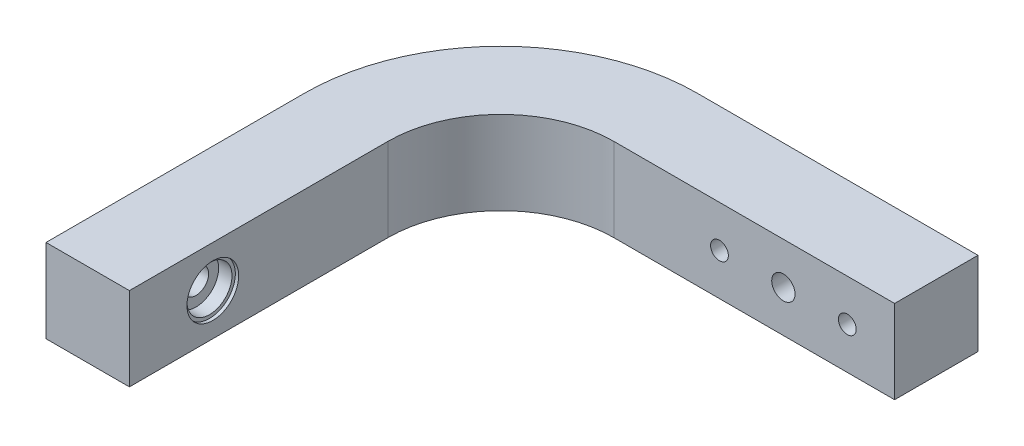
SolidWorks part; units mm, degrees
ref_plane "Front Plane" through (0, 0, 0) normal (0, 0, 1) x (1, 0, 0)
ref_plane "Top Plane" through (0, 0, 0) normal (0, 1, 0) x (1, 0, 0)
ref_plane "Right Plane" through (0, 0, 0) normal (1, 0, 0) x (0, 0, -1)
ref_axis "Z" through (0, 0, -59.2654) along (0, 0, 1)
sketch "Sketch1" plane through (0, 0, 0) normal (0, 1, 0) x (1, 0, 0)
  line L0 (-30.4827, 0) -> (30.4827, 0) construction
  line L1 (-65.8046, -35.3218) -> (-65.8046, -81.8046)
  line L2 (-65.8046, -81.8046) -> (-50.8046, -81.8046)
  line L3 (-50.8046, -81.8046) -> (-50.8046, -35.3218)
  line L4 (-30.4827, -15) -> (30.4827, -15) construction
  line L5 (0, -15) -> (0, 0) construction
  line L6 (50.8046, -81.8046) -> (50.8046, -35.3218) construction
  line L7 (65.8046, -81.8046) -> (50.8046, -81.8046) construction
  line L8 (65.8046, -35.3218) -> (65.8046, -81.8046) construction
  line L9 (30.4827, 0) -> (30.4827, -15) construction
  line L10 (20, -15) -> (20, 0)
  line L11 (-30.4827, -15) -> (20, -15)
  line L12 (-30.4827, 0) -> (20, 0)
  line L13 (0, 59.2654) -> (0, -30.9346) construction
  arc A0 (-30.4827, 0) -> (-65.8046, -35.3218) centre (-30.4827, -35.3218) ccw
  arc A1 (-50.8046, -35.3218) -> (-30.4827, -15) centre (-30.4827, -35.3218) cw
  arc A2 (50.8046, -35.3218) -> (30.4827, -15) centre (30.4827, -35.3218) ccw construction
  arc A3 (30.4827, 0) -> (65.8046, -35.3218) centre (30.4827, -35.3218) cw construction
  dimension "D3" = 20.3218
  dimension "D1" = 101.6092
  dimension "D2" = 15
  dimension "D4" = 66.8046
  dimension "D5" = 20
extrude "Boss-Extrude1" add sketch "Sketch1" along normal blind 7.5 and the other way blind 7.5
sketch "Sketch2" plane through (-50.8046, 0, 0) normal (-1, 0, 0) x (0, 0, 1)
  line L1 (45.1, 0) -> (-45.1, 0) construction
  line L2 (0, -8.25) -> (0, 8.25) construction
  circle A0 centre (66.8046, 0) radius 2.25
  dimension "D1" = 4.5
  dimension "D2" = 66.8046
extrude "Cut-Extrude1" cut sketch "Sketch2" against normal through all both and the other way through all
ref_axis "Axis2" through (-85.4136, 0, 66.8046) along (1, 0, 0)
sketch "Sketch3" plane through (0, 0, 0) normal (0, 0, -1) x (-1, 0, 0)
  line L0 (-11.5, 0) -> (11.5, 0) construction
  circle A0 centre (0, 0) radius 2.1
  circle A1 centre (-11.5, 0) radius 1.6
  circle A2 centre (11.5, 0) radius 1.6
  dimension "D1" = 4.2
  dimension "D3" = 3.2
  dimension "D2" = 23
extrude "Cut-Extrude2" cut sketch "Sketch3" against normal through all
sketch "Sketch5" plane through (0, 0, 0) normal (0, 1, 0) x (1, 0, 0)
  line L0 (-65.8046, -71.4546) -> (-65.2046, -71.4546)
  line L1 (-65.2046, -71.4546) -> (-65.2046, -70.8546)
  line L2 (-65.2046, -70.8546) -> (-62.8046, -70.8546)
  line L3 (-62.8046, -70.8546) -> (-62.8046, -66.8046)
  line L4 (-65.8046, -71.4546) -> (-65.8046, -66.8046)
  line L5 (-85.4136, -66.8046) -> (-36.6951, -66.8046) construction
  line L6 (-84.3923, -66.8046) -> (-79.5242, -66.8046) construction
  line L7 (-65.8046, -66.8046) -> (-62.8046, -66.8046)
  line L9 (-65.8046, -35.3218) -> (-65.8046, -81.8046) construction
  line L10 (-58.3046, -77.8481) -> (-58.3046, -69.6196) construction
  line L11 (-65.8046, -81.8046) -> (-50.8046, -81.8046) construction
  line L12 (-50.8046, -66.8046) -> (-53.8046, -66.8046)
  line L13 (-50.8046, -71.4546) -> (-50.8046, -66.8046)
  line L14 (-53.8046, -70.8546) -> (-53.8046, -66.8046)
  line L15 (-51.4046, -70.8546) -> (-53.8046, -70.8546)
  line L16 (-51.4046, -71.4546) -> (-51.4046, -70.8546)
  line L17 (-50.8046, -71.4546) -> (-51.4046, -71.4546)
  point P14 (-58.3046, -81.8046)
  dimension "D1" = 0.6
  dimension "D2" = 4.65
  dimension "D3" = 8.1
  dimension "D4" = 3
revolve "bearing-seats" cut sketch "Sketch5" angle 360 about L6
equation "\"width\"= \"EyeDiameter\" + \"EyeClearance\""
equation "\"prongwidth\"= \"L2Thickness\""
equation "\"D2@Sketch1\"=\"prongwidth\""
equation "\"D3@Sketch1\"=\"width\"/5"
equation "\"pronglength\"= \"BasePlaneDistance\"'model implicitly adds clearance (of prongwidth) to the hole drilled at the baseplanedistance"
equation "\"D4@Sketch1\"=\"pronglength\""
equation "\"D1@Boss-Extrude1\"=\"prongwidth\"/2"
equation "\"D2@Boss-Extrude1\"=\"prongwidth\"/2"
equation "\"lbracket-plane-to-axis\"= \"BasePlaneDistance\""
equation "\"D2@Sketch2\"=\"lbracket-plane-to-axis\""
equation "\"EyeDiameter\" = 99.60916292"
equation "\"BasePlaneDistance\" = \"EyeDiameter\"/2+\"L2Thickness\"+\"EyeClearance\""
equation "\"EyeClearance\" = 2"
equation "\"D1@Sketch1\"=\"EyeDiameter\"+\"EyeClearance\""
equation "\"BearingDepth\"= 6"
equation "\"BearingHousingID\"=4.5"
equation "\"BearingFlangeThickness\"= 0.75"
equation "\"BearingFlangeOD\"=7.5"
equation "\"PrinterFilamentThickness\"= 0.1"
equation "\"ApplyPrinterOffset\"= 1'if 1, adjust hole sizes to try and make pressfits work with the 3d printer"
equation "\"L2Thickness\" = 3.75 * \"shaft_diameter\""
equation "\"L2_ID\" = 20"
equation "\"vx\" = 50"
equation "\"vy\" = 10"
equation "\"vz\" = 100"
equation "\"parametric_end\" = 1"
equation "\"Rw_3_xx\" = -(\"vz\")/sqr((\"vx\")^2 + (\"vz\")^2)"
equation "\"Rw_3_xy\" = 0"
equation "\"Rw_3_xz\" = (\"vx\")/sqr((\"vx\")^2 + (\"vz\")^2)"
equation "\"Rw_3_zx\" = (\"vx\")/sqr((\"vx\")^2 + (\"vy\")^2 + (\"vz\")^2)"
equation "\"Rw_3_zy\" = (\"vy\")/sqr((\"vx\")^2 + (\"vy\")^2 + (\"vz\")^2)"
equation "\"Rw_3_zz\" = (\"vz\")/sqr((\"vx\")^2 + (\"vy\")^2 + (\"vz\")^2)"
equation "\"Rw_3_yx\" = (\"vx\")*(\"vy\")/sqr((\"vx\")^4 + (\"vx\")^2*(\"vy\")^2 + 2*(\"vx\")^2*(\"vz\")^2 + (\"vy\")^2*(\"vz\")^2 + (\"vz\")^4)"
equation "\"Rw_3_yy\" = -sqr((\"vx\")^2 + (\"vz\")^2)/sqr((\"vx\")^2 + (\"vy\")^2 + (\"vz\")^2)"
equation "\"Rw_3_yz\" = (\"vy\")*(\"vz\")/sqr((\"vx\")^4 + (\"vx\")^2*(\"vy\")^2 + 2*(\"vx\")^2*(\"vz\")^2 + (\"vy\")^2*(\"vz\")^2 + (\"vz\")^4)"
equation "\"O2Targx\" = -\"BasePlaneDistance\"*(\"vx\")*(\"vy\")/sqr((\"vx\")^4 + (\"vx\")^2*(\"vy\")^2 + 2*(\"vx\")^2*(\"vz\")^2 + (\"vy\")^2*(\"vz\")^2 + (\"vz\")^4)"
equation "\"O2Targy\" = \"BasePlaneDistance\"*sqr((\"vx\")^2 + (\"vz\")^2)/sqr((\"vx\")^2 + (\"vy\")^2 + (\"vz\")^2)"
equation "\"O2Targz\" = -\"BasePlaneDistance\"*(\"vy\")*(\"vz\")/sqr((\"vx\")^4 + (\"vx\")^2*(\"vy\")^2 + 2*(\"vx\")^2*(\"vz\")^2 + (\"vy\")^2*(\"vz\")^2 + (\"vz\")^4)"
equation "\"O2Targx_0\" = -(\"BasePlaneDistance\")*sqr((\"vx\")^2 + (\"vz\")^2)/sqr((\"vx\")^2 + (\"vy\")^2 + (\"vz\")^2)"
equation "\"O2Targy_0\" = -(\"BasePlaneDistance\")*(\"vy\")*(\"vz\")/sqr((\"vx\")^4 + (\"vx\")^2*(\"vy\")^2 + 2*(\"vx\")^2*(\"vz\")^2 + (\"vy\")^2*(\"vz\")^2 + (\"vz\")^4)"
equation "\"O2Targz_0\" = (\"BasePlaneDistance\")*(\"vx\")*(\"vy\")/sqr((\"vx\")^4 + (\"vx\")^2*(\"vy\")^2 + 2*(\"vx\")^2*(\"vz\")^2 + (\"vy\")^2*(\"vz\")^2 + (\"vz\")^4) + (\"BasePlaneDistance\")"
equation "\"theta2_s1\" = arcsin(((\"BasePlaneDistance\") - (\"O2Targz_0\"))/(\"BasePlaneDistance\")) + pi"
equation "\"theta2_s2\" = -arcsin(((\"BasePlaneDistance\") - (\"O2Targz_0\"))/(\"BasePlaneDistance\"))"
equation "\"theta1_s1\" = arcsin((\"O2Targy_0\")/((\"BasePlaneDistance\")*cos((\"Theta2\")))) + pi"
equation "\"theta1_s2\" = -arcsin((\"O2Targy_0\")/((\"BasePlaneDistance\")*cos((\"Theta2\"))))"
equation "\"theta1_s3\" = -arccos(-(\"O2Targx_0\")/((\"BasePlaneDistance\")*cos((\"Theta2\")))) + 2*pi"
equation "\"theta1_s4\" = arccos(-(\"O2Targx_0\")/((\"BasePlaneDistance\")*cos((\"Theta2\"))))"
equation "\"Theta1\" = \"theta1_s2\" 'so far, theta1_s1 and theta1_s4 have agreed, and they agree with the sw constraint solver"
equation "\"Theta2\" = \"theta2_s2\""
equation "\"o2_x\" = -(\"BasePlaneDistance\")*cos((\"Theta1\"))*cos((\"Theta2\"))"
equation "\"o2_y\" = -(\"BasePlaneDistance\")*sin((\"Theta1\"))*cos((\"Theta2\"))"
equation "\"o2_z\" = (\"BasePlaneDistance\")*(sin((\"Theta2\")) + 1)"
equation "\"o1_x\" = (\"BasePlaneDistance\")*sin((\"Theta1\"))"
equation "\"o1_y\" = -(\"BasePlaneDistance\")*cos((\"Theta1\"))"
equation "\"o1_z\" = (\"BasePlaneDistance\")"
equation "\"Actuator1_Theta\" = atn(\"vx\"/\"vz\") 'ik solution for the single link joint"
equation "\"Actuator2_Theta\" = \"Theta1\"  'ik solution for the double link joint"
equation "\"MotorBaseThickness\" = 3 "
equation "\"BaseThickness\" = 3 "
equation "\"EncoderToMagnetAirgap\" = 1 'Encoder to magnet airgap"
equation "\"EncoderHeight\" = 1.192  'Height of the encoder"
equation "\"MagnetThickness\" = 0.5  'Magnet thickness"
equation "\"pcb_thickness\" = 1.6  'Thickness of the PCB"
equation "\"pcb_outer_diameter\" = 32 'the OD of the pcb"
equation "\"shaft_diameter\" = 4"
equation "\"D1@Sketch2\"=\"shaft_diameter\"*1.125"
equation "\"D2@Sketch5\"=\"ApplyPrinterOffset\" * \"PrinterFilamentThickness\" / 2 + 4.6"
equation "\"D3@Sketch5\"= \"ApplyPrinterOffset\" * \"PrinterFilamentThickness\"  + 8.00"
